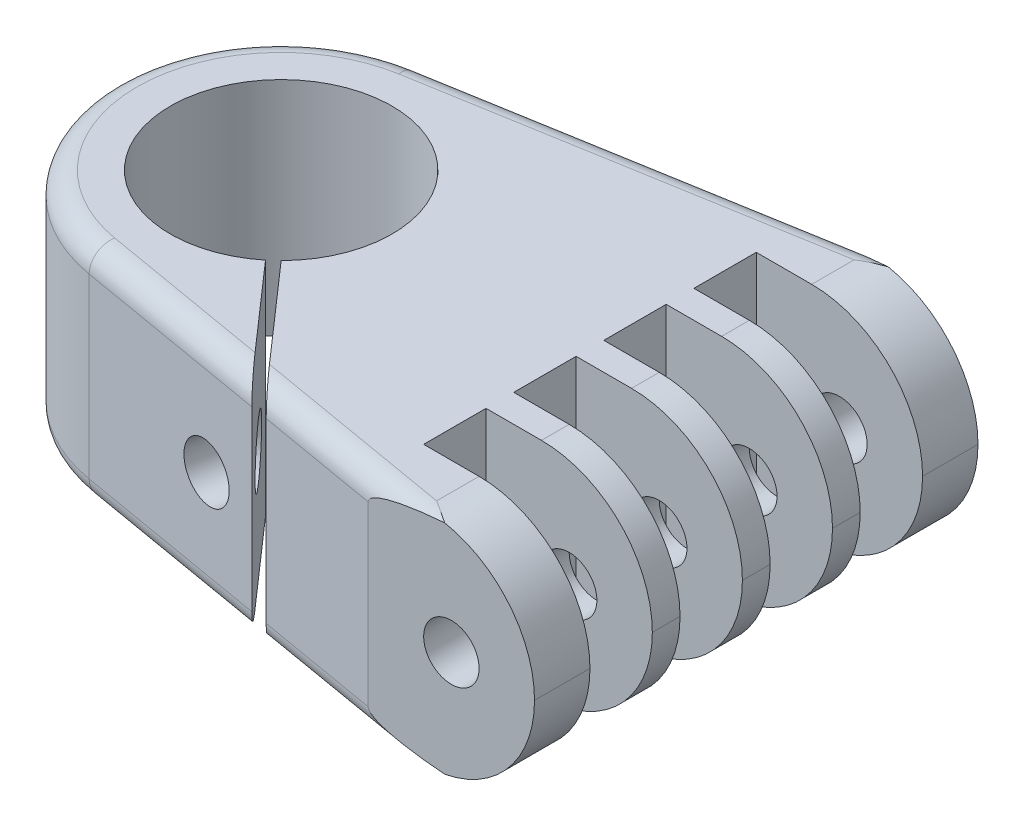
SolidWorks part; units mm, degrees
ref_plane "Front Plane" through (0, 0, 0) normal (0, 0, 1) x (1, 0, 0)
ref_plane "Top Plane" through (0, 0, 0) normal (0, 1, 0) x (1, 0, 0)
ref_plane "Right Plane" through (0, 0, 0) normal (1, 0, 0) x (0, 0, -1)
sketch "Sketch1" plane through (0, 0, 0) normal (0, 1, 0) x (1, 0, 0)
  line L0 (27.8497, 15) -> (27.8497, 9.375)
  line L1 (-2.5377, 14.7838) -> (27.8497, 20)
  line L2 (-2.5377, -14.7838) -> (15.1764, -17.8245)
  line L3 (27.8497, 20) -> (42.8497, 20)
  line L4 (42.8497, 20) -> (42.8497, 15)
  line L5 (42.8497, -20) -> (27.8497, -20)
  line L6 (42.8497, 15) -> (27.8497, 15)
  line L7 (27.8497, 1.25) -> (42.8497, 1.25)
  line L8 (27.8497, -1.25) -> (42.8497, -1.25)
  line L9 (27.8497, -6.875) -> (42.8497, -6.875)
  line L10 (27.8497, -9.375) -> (42.8497, -9.375)
  line L11 (27.8497, -15) -> (42.8497, -15)
  line L12 (27.8497, 9.375) -> (42.8497, 9.375)
  line L13 (42.8497, 6.875) -> (27.8497, 6.875)
  line L14 (42.8497, 9.375) -> (42.8497, 6.875)
  line L15 (42.8497, 1.25) -> (42.8497, -1.25)
  line L16 (42.8497, -6.875) -> (42.8497, -9.375)
  line L17 (42.8497, -15) -> (42.8497, -20)
  line L18 (7.0698, -7.0724) -> (16.743, -18.0935)
  line L19 (6.3182, -7.732) -> (15.1764, -17.8245)
  line L20 (6.3182, -7.732) -> (15.9915, -18.7531) construction
  line L21 (16.743, -18.0935) -> (27.8497, -20)
  line L22 (27.8497, 6.875) -> (27.8497, 1.25)
  line L23 (27.8497, -1.25) -> (27.8497, -6.875)
  line L24 (27.8497, -9.375) -> (27.8497, -15)
  arc A0 (7.0698, -7.0724) -> (6.328, -7.7432) centre (0, 0) ccw
  arc A1 (-2.5377, 14.7838) -> (-2.5377, -14.7838) centre (0, 0) ccw
  dimension "D1" = 20
  dimension "D2" = 30
  dimension "D3" = 40
  dimension "D4" = 5
  dimension "D5" = 2.5
  dimension "D6" = 2.5
  dimension "D7" = 5
  dimension "D8" = 2.5
  dimension "D9" = 5.625
  dimension "D10" = 5.625
  dimension "D11" = 5.625
  dimension "D12" = 1
  dimension "D13" = 15
extrude "Boss-Extrude1" add sketch "Sketch1" along normal blind 20 contours L1 A1 L2 L19 A0 L18 L21 L5 L17 L11 L24 L10 L16 L9 L23 L8 L15 L7 L22 L13 L14 L12 L0 L6 L4 L3 region at (16.6641, 0, -0.1403)
fillet "Fillet1" radius 10 10 edges at (42.8497, 0, 17.5) (42.8497, 0, 8.125) (42.8497, 0, 0) (42.8497, 0, -8.125) (42.8497, 0, -17.5) (42.8497, 20, -17.5) (42.8497, 20, -8.125) (42.8497, 20, 0) (42.8497, 20, 8.125) (42.8497, 20, 17.5)
sketch "Sketch2" plane through (0, 0, -20) normal (0, 0, -1) x (-1, 0, 0)
  circle A0 centre (-35.3497, 10) radius 2.5
  dimension "D1" = 5
  dimension "D2" = 7.5
extrude "Cut-Extrude1" cut sketch "Sketch2" against normal blind 40
fillet "Fillet2" radius 2 8 edges at (12.656, 0, -17.3919) (6.3193, 0, 16.3042) (12.656, 20, -17.3919) (6.3193, 20, 16.3042) (22.2964, 0, 19.0467) (22.2964, 20, 19.0467) (-15, 0, 0) (-15, 20, 0)
sketch "Sketch3" plane through (-2.5377, 0, 14.7838) normal (-0.1692, 0, 0.9856) x (0.9856, 0, 0.1692)
  line L0 (17.9733, 18) -> (17.9733, 2) construction
  circle A0 centre (12.9733, 10) radius 2.5
  dimension "D1" = 5
  dimension "D2" = 5
extrude "Cut-Extrude2" cut sketch "Sketch3" against normal blind 10
